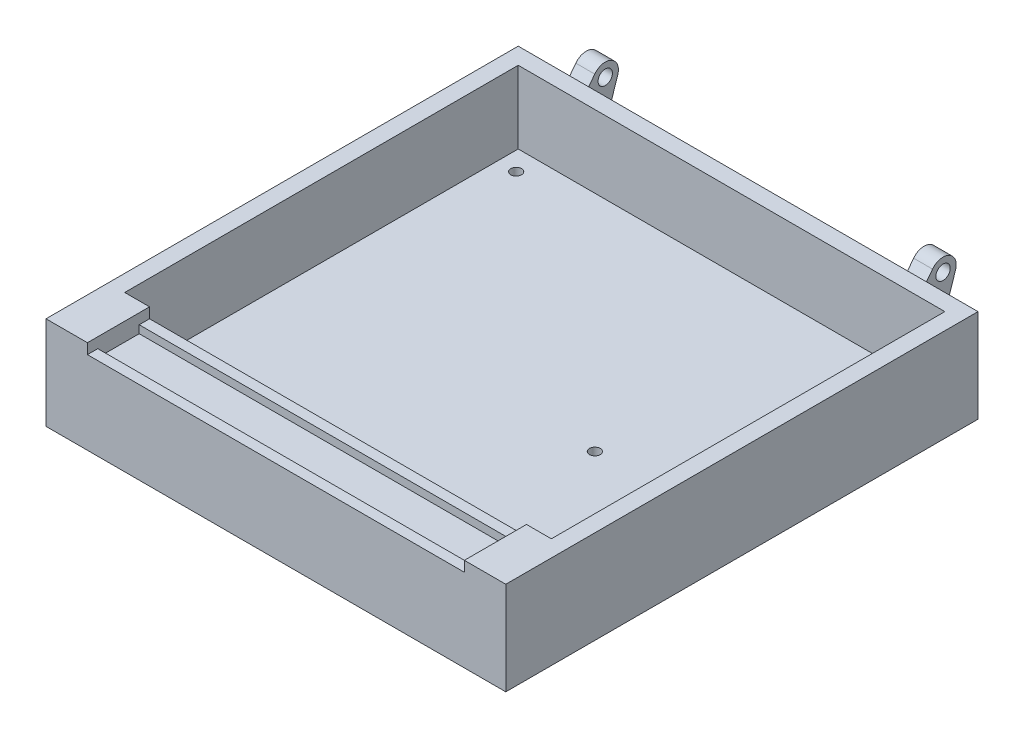
SolidWorks part; units mm, degrees
ref_plane "Front Plane" through (0, 0, 0) normal (0, 0, 1) x (1, 0, 0)
ref_plane "Top Plane" through (0, 0, 0) normal (0, 1, 0) x (1, 0, 0)
ref_plane "Right Plane" through (0, 0, 0) normal (1, 0, 0) x (0, 0, -1)
sketch "Sketch1" plane through (0, 0, 0) normal (0, 1, 0) x (1, 0, 0)
  line L1 (-65.405, -57.15) -> (65.405, -57.15) construction
  line L2 (-65.405, -57.15) -> (-65.405, 57.15) construction
  line L3 (-65.405, 57.15) -> (65.405, 57.15) construction
  line L4 (65.405, -57.15) -> (65.405, 57.15) construction
  line L5 (-65.405, -57.15) -> (65.405, 57.15) construction
  line L6 (-65.405, 57.15) -> (65.405, -57.15) construction
  line L7 (-70.485, 62.23) -> (70.485, 62.23)
  line L8 (-70.485, 62.23) -> (-70.485, -82.55)
  line L9 (-70.485, -82.55) -> (70.485, -82.55)
  line L10 (70.485, 62.23) -> (70.485, -82.55)
  circle A0 centre (61.595, 50.8) radius 1.65
  circle A1 centre (-59.69, 50.8) radius 1.65
  circle A2 centre (26.67, -11.43) radius 1.65
  point P0 (0, 0)
  point P16 (0, 0)
  dimension "D5" = 3.3
  dimension "D1" = 114.3
  dimension "D2" = 130.81
  dimension "D3" = 92.075
  dimension "D4" = 127
  dimension "D6" = 5.08
  dimension "D7" = 5.08
  dimension "D8" = 5.08
  dimension "D9" = 107.95
  dimension "D10" = 5.715
  dimension "D11" = 45.72
  dimension "D12" = 25.4
extrude "Boss-Extrude1" add sketch "Sketch1" along normal blind 6.35
sketch "Sketch2" plane through (0, 6.35, 0) normal (0, 1, 0) x (1, 0, 0)
  line L0 (70.485, -82.55) -> (70.485, 62.23) construction
  line L2 (-70.485, 62.23) -> (-70.485, -82.55) construction
  line L3 (70.485, 62.23) -> (-70.485, 62.23) construction
  line L4 (70.485, -82.55) -> (70.485, 62.23)
  line L5 (-70.485, -82.55) -> (70.485, -82.55)
  line L6 (-70.485, 62.23) -> (-70.485, -82.55)
  line L7 (70.485, 62.23) -> (-70.485, 62.23)
  line L8 (57.785, -79.375) -> (57.785, -66.675)
  line L9 (65.405, 57.15) -> (-65.405, 57.15)
  line L10 (-65.405, 57.15) -> (-65.405, -63.5)
  line L12 (-65.405, -63.5) -> (65.405, -63.5)
  line L13 (-57.785, -79.375) -> (57.785, -79.375)
  line L14 (57.785, -66.675) -> (-57.785, -66.675)
  line L15 (-57.785, -66.675) -> (-57.785, -79.375)
  line L16 (65.405, -63.5) -> (65.405, 57.15)
  dimension "D2" = 3.175
  dimension "D1" = 5.08
  dimension "D3" = 5.08
  dimension "D4" = 5.08
  dimension "D5" = 12.7
  dimension "D6" = 3.175
  dimension "D7" = 12.7
  dimension "D8" = 12.7
extrude "Boss-Extrude2" add sketch "Sketch2" along normal blind 22.225
sketch "Sketch3" plane through (0, 28.575, 0) normal (0, 1, 0) x (1, 0, 0)
  line L0 (-65.405, -63.5) -> (65.405, -63.5) construction
  line L1 (-57.785, -63.5) -> (57.785, -63.5)
  line L2 (-57.785, -63.5) -> (-57.785, -82.55)
  line L3 (-57.785, -82.55) -> (57.785, -82.55)
  line L4 (57.785, -63.5) -> (57.785, -82.55)
  line L5 (-70.485, -82.55) -> (70.485, -82.55) construction
  line L7 (57.785, -79.375) -> (57.785, -66.675) construction
  line L8 (-57.785, -66.675) -> (-57.785, -79.375) construction
extrude "Cut-Extrude1" cut sketch "Sketch3" against normal blind 3.175
sketch "Sketch4" plane through (0, 6.35, 0) normal (0, 1, 0) x (1, 0, 0)
  line L4 (-57.785, -66.675) -> (-57.785, -79.375)
  line L5 (-57.785, -79.375) -> (57.785, -79.375)
  line L6 (57.785, -79.375) -> (57.785, -66.675)
  line L7 (57.785, -66.675) -> (-57.785, -66.675)
  line L8 (-57.785, -66.675) -> (-57.785, -79.375)
  line L9 (-57.785, -79.375) -> (57.785, -79.375)
  line L10 (57.785, -79.375) -> (57.785, -66.675)
  line L11 (57.785, -66.675) -> (-57.785, -66.675)
  dimension "D1" = 0
extrude "Boss-Extrude3" add sketch "Sketch4" along normal offset from surface (16.6687 mm away) 2.3813 up to face at (0, 25.4, 65.0875)
ref_plane "Plane1" through (51.7855, 0, 0) normal (1, 0, 0) x (0, 0, -1)
sketch "Sketch5" plane through (51.7855, 0, 0) normal (1, 0, 0) x (0, 0, -1)
  line L0 (-82.55, 28.575) -> (62.23, 28.575) construction
  line L1 (69.3307, 32.075) -> (65.2893, 32.075) construction
  line L2 (65.2893, 32.075) -> (63.2685, 28.575) construction
  line L3 (63.2685, 28.575) -> (65.2893, 25.075) construction
  line L4 (65.2893, 25.075) -> (69.3307, 25.075) construction
  line L5 (69.3307, 25.075) -> (71.3515, 28.575) construction
  line L6 (71.3515, 28.575) -> (69.3307, 32.075) construction
  line L7 (62.23, 28.575) -> (62.23, 0) construction
  line L8 (62.23, 28.575) -> (64.0948, 31.0236)
  line L9 (62.23, 0) -> (62.23, 28.575)
  line L10 (62.23, 0) -> (71.1518, 27.3204)
  circle A0 centre (67.31, 28.575) radius 3.5 construction
  arc A1 (64.0948, 31.0236) -> (71.1518, 27.3204) centre (67.31, 28.575) cw
  circle A2 centre (67.31, 28.575) radius 2.2
  dimension "D3" = 4.4
  dimension "D1" = 5.08
  dimension "D2" = 7
extrude "Boss-Extrude4" add sketch "Sketch5" along normal mid plane 5.8
mirror "Mirror1" about plane through (0, 0, 0) normal (1, 0, 0) of "Boss-Extrude4"
